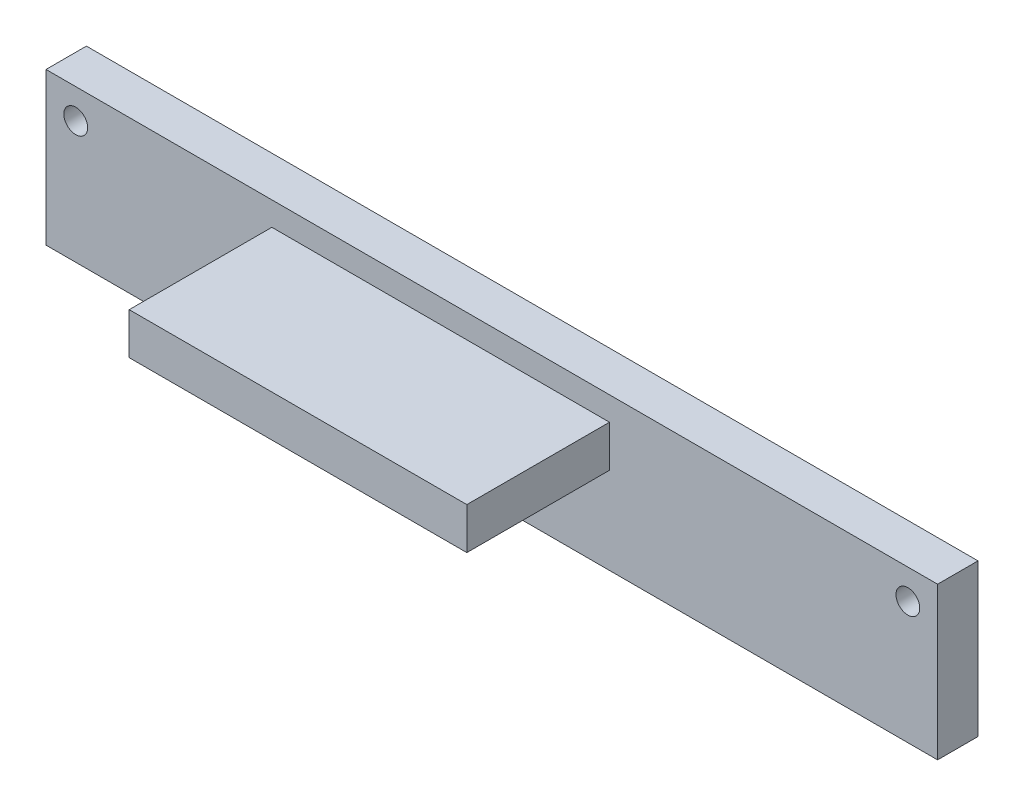
SolidWorks part; units mm, degrees
ref_plane "Front Plane" through (0, 0, 0) normal (0, 0, 1) x (1, 0, 0)
ref_plane "Top Plane" through (0, 0, 0) normal (0, 1, 0) x (1, 0, 0)
ref_plane "Right Plane" through (0, 0, 0) normal (1, 0, 0) x (0, 0, -1)
sketch "Sketch1" plane through (0, 0, 0) normal (0, 0, 1) x (1, 0, 0)
  line L1 (0, 0) -> (75, 0)
  line L2 (0, 0) -> (0, 12.8)
  line L3 (0, 12.8) -> (75, 12.8)
  line L4 (75, 0) -> (75, 12.8)
  dimension "D1" = 75
  dimension "D2" = 12.8
extrude "Boss-Extrude1" add sketch "Sketch1" along normal blind 3.4
sketch "Sketch2" plane through (0, 0, 3.4) normal (0, 0, 1) x (1, 0, 0)
  line L0 (0, 12.8) -> (0, 0) construction
  line L1 (19, 10.8) -> (47.4, 10.8)
  line L2 (19, 10.8) -> (19, 7.3)
  line L3 (19, 7.3) -> (47.4, 7.3)
  line L4 (47.4, 10.8) -> (47.4, 7.3)
  line L6 (75, 12.8) -> (0, 12.8) construction
  line L7 (75, 0) -> (75, 12.8) construction
  circle A0 centre (2.5, 10.3) radius 1.001
  circle A1 centre (72.5, 10.3) radius 1
  dimension "D4" = 2
  dimension "D6" = 2.5
  dimension "D1" = 3.5
  dimension "D2" = 28.4
  dimension "D3" = 19
  dimension "D5" = 2.5
  dimension "D7" = 2.5
  dimension "D8" = 2.5
extrude "Boss-Extrude2" add sketch "Sketch2" along normal blind 12 contours L4 L1 L2 L3 region at (33.2, 9.05, 3.4)
extrude "Cut-Extrude1" cut sketch "Sketch2<3>" against normal blind 12 contours A1 | A0 region at (72.5, 10.3, 3.4)
sketch "Sketch2<3>" plane through (0, 0, 3.4) normal (0, 0, 1) x (1, 0, 0) same geometry as "Sketch2"
